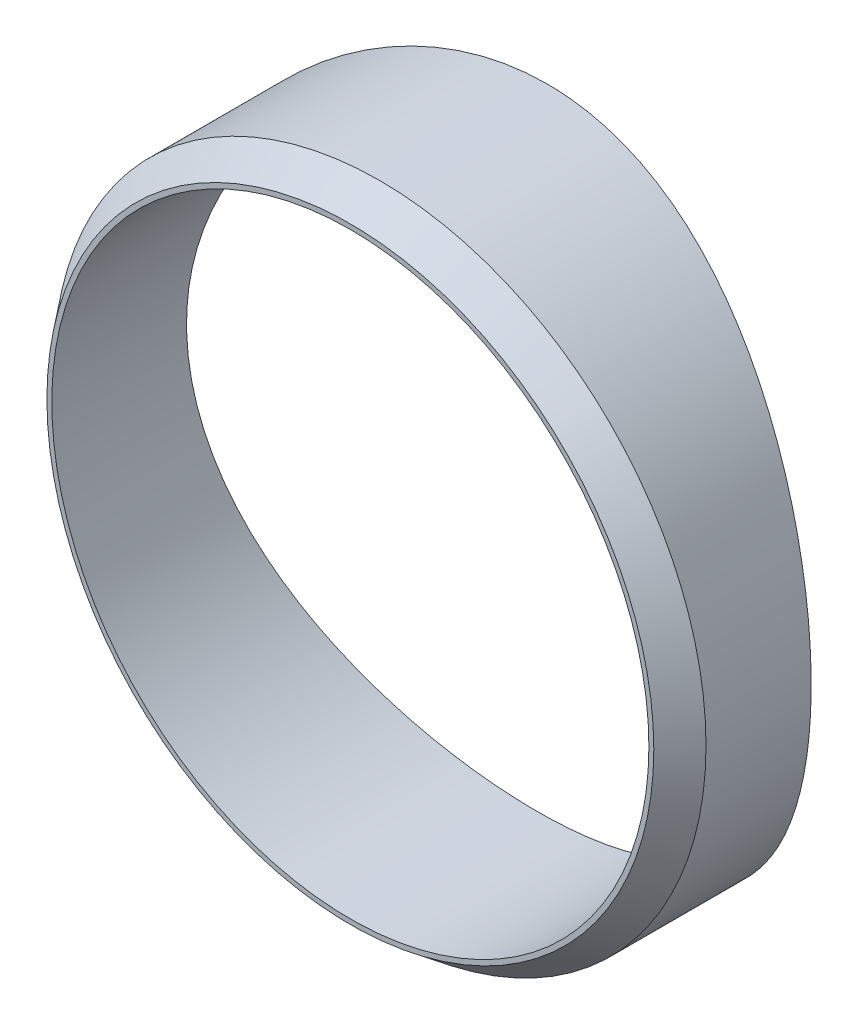
SolidWorks part; units mm, degrees
material "Plain Carbon Steel"
ref_plane "Front Plane" through (0, 0, 0) normal (0, 0, 1) x (1, 0, 0)
ref_plane "Top Plane" through (0, 0, 0) normal (0, 1, 0) x (1, 0, 0)
ref_plane "Right Plane" through (0, 0, 0) normal (1, 0, 0) x (0, 0, -1)
sketch "Sketch1" plane through (0, 0, 0) normal (0, 0, 1) x (1, 0, 0)
  circle A0 centre (0, 0) radius 84.1375
  circle A1 centre (0, 0) radius 77.0255
  dimension "D1" = 168.275
  dimension "D2" = 7.112
extrude "Extrude1" add sketch "Sketch1" along normal mid plane 50.8
ref_plane "Plane-Origin" through (0, 0, 0) normal (0, 0, 1) x (1, 0, 0)
ref_axis "Axis1" through (0, 0, 25.4) along (0, 0, -1)
chamfer "Chamfer1" distance 7.62 angle 37.5 1 edges at (84.1375, 0, 25.4) first distance on face at (84.1375, 0, 25.4)
sketch "Sketch2" plane through (0, 0, 0) normal (1, 0, 0) x (0, 0, -1)
  line L0 (9.3531, 0) -> (466.5531, 0) construction
  line L1 (25.4, 84.1375) -> (25.4, 107.7434) construction
  line L4 (25.4, 84.1375) -> (25.4, -84.1375)
  arc A0 (25.4, 84.1375) -> (25.4, -84.1375) centre (237.9531, 0) ccw
extrude "Cut-Extrude1" cut sketch "Sketch2" against normal through all
extrude "Cut-Extrude2" cut sketch "Sketch2<2>" against normal through all both and the other way through all
sketch "Sketch2<2>" plane through (0, 0, 0) normal (1, 0, 0) x (0, 0, -1) same geometry as "Sketch2"
